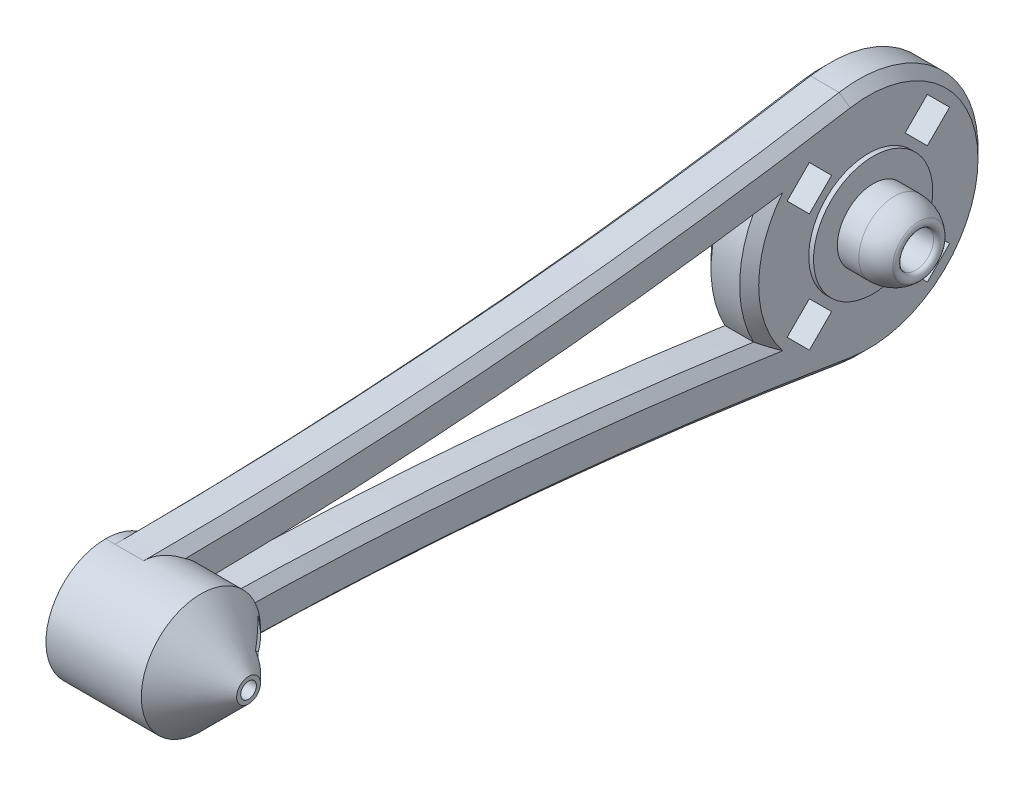
SolidWorks part; units mm, degrees
ref_plane "Front Plane" through (0, 0, 0) normal (0, 0, 1) x (1, 0, 0)
ref_plane "Top Plane" through (0, 0, 0) normal (0, 1, 0) x (1, 0, 0)
ref_plane "Right Plane" through (0, 0, 0) normal (1, 0, 0) x (0, 0, -1)
sketch "Sketch1" plane through (0, 0, 0) normal (1, 0, 0) x (0, 0, -1)
  line L0 (-150, 0) -> (0, 0) construction
  arc A0 (-4.1379, -24.6552) -> (-4.1379, 24.6552) centre (0, 0) ccw
  arc A1 (-150, 12.5) -> (-150, -12.5) centre (-150, 0) ccw
  arc A2 (-150, 12.5) -> (-4.1379, 24.6552) centre (-150, 893.75) ccw
  arc A3 (-150, -12.5) -> (-4.1379, -24.6552) centre (-150, -893.75) cw
  arc A4 (-150, 12.5) -> (-150, -12.5) centre (-150, 0) cw construction
  arc A5 (-4.1379, 24.6552) -> (-4.1379, -24.6552) centre (0, 0) ccw construction
  arc A6 (-137.77, -2.5839) -> (-22.0783, -11.7281) centre (-150, -893.75) cw
  arc A7 (-150, 2.5) -> (-2.4828, 14.7931) centre (-150, 893.75) ccw construction
  arc A8 (-137.77, 2.5839) -> (-22.0783, 11.7281) centre (-150, 893.75) ccw
  arc A9 (-137.77, 2.5839) -> (-137.77, -2.5839) centre (-150, 0) cw
  arc A10 (-150, -2.5) -> (-2.4828, -14.7931) centre (-150, -893.75) cw construction
  arc A11 (-2.4828, -14.7931) -> (-2.4828, 14.7931) centre (0, 0) ccw construction
  arc A12 (-150, 2.5) -> (-150, -2.5) centre (-150, 0) ccw construction
  arc A13 (-22.0783, 11.7281) -> (-22.0783, -11.7281) centre (0, 0) ccw
  dimension "D1" = 150
  dimension "D2" = 50
  dimension "D3" = 25
  dimension "D4" = 10
extrude "Boss-Extrude1" add sketch "Sketch1" along normal blind 10
sketch "Sketch2" plane through (10, 0, 0) normal (1, 0, 0) x (0, 0, -1)
  circle A0 centre (0, 0) radius 12.5
  dimension "D1" = 25
extrude "Boss-Extrude2" add sketch "Sketch2" along normal blind 1
sketch "Sketch3" plane through (11, 0, 0) normal (1, 0, 0) x (0, 0, -1)
  circle A0 centre (0, 0) radius 7.5
  dimension "D1" = 15
extrude "Boss-Extrude3" add sketch "Sketch3" along normal blind 12
fillet "Fillet1" radius 7.5 1 edges at (23, 0, -7.5)
sketch "Sketch4" plane through (10, 0, 0) normal (1, 0, 0) x (0, 0, -1)
  line L0 (0, 0) -> (0, 17.5) construction
  circle A0 centre (-12.3744, 12.3744) radius 2
  circle A1 centre (0, 0) radius 17.5 construction
  circle A2 centre (12.3744, 12.3744) radius 2
  circle A3 centre (12.3744, -12.3744) radius 2
  circle A4 centre (-12.3744, -12.3744) radius 2
  point P15 (0, 0)
  dimension "D1" = 35
  dimension "D3" = 4
  dimension "D2" = 45
  dimension "D4" = 4
extrude "Cut-Extrude1" cut sketch "Sketch4" against normal through all
sketch "Sketch5" plane through (10, 0, 0) normal (1, 0, 0) x (0, 0, -1)
  line L0 (-17.0413, 12.3744) -> (-12.3744, 7.7075)
  line L1 (-12.3744, 7.7075) -> (-7.7075, 12.3744)
  line L2 (-7.7075, 12.3744) -> (-12.3744, 17.0413)
  line L3 (-12.3744, 17.0413) -> (-17.0413, 12.3744)
  line L4 (-17.0413, 12.3744) -> (-7.7075, 12.3744) construction
  line L5 (-12.3744, 17.0413) -> (-12.3744, 7.7075) construction
  line L6 (-14.7078, 10.0409) -> (-10.0409, 14.7078) construction
  line L7 (7.7075, 12.3744) -> (12.3744, 7.7075)
  line L8 (12.3744, 7.7075) -> (17.0413, 12.3744)
  line L9 (17.0413, 12.3744) -> (12.3744, 17.0413)
  line L10 (12.3744, 17.0413) -> (7.7075, 12.3744)
  line L11 (12.3744, -7.7075) -> (7.7075, -12.3744)
  line L12 (7.7075, -12.3744) -> (12.3744, -17.0413)
  line L13 (12.3744, -17.0413) -> (17.0413, -12.3744)
  line L14 (17.0413, -12.3744) -> (12.3744, -7.7075)
  line L15 (-7.7075, -12.3744) -> (-12.3744, -7.7075)
  line L16 (-12.3744, -7.7075) -> (-17.0413, -12.3744)
  line L17 (-17.0413, -12.3744) -> (-12.3744, -17.0413)
  line L18 (-12.3744, -17.0413) -> (-7.7075, -12.3744)
  circle A0 centre (0, 0) radius 17.5 construction
  point P8 (-12.3744, 12.3744)
  point P25 (0, 0)
  dimension "D1" = 6.6
  dimension "D2" = 4
extrude "Cut-Extrude2" cut sketch "Sketch5" against normal blind 5
chamfer "Chamfer1" distance 2 angle 45 16 edges at (0, 0, 137.5) (0, -5.2709, 79.7751) (0, 0, 25) (0, 5.2709, 79.7751) (0, -15.5441, 76.8162) (0, 0, -25) (0, 0, 162.5) (0, 15.5441, 76.8162) (10, 15.5441, 76.8162) (10, 0, 162.5) (10, 0, -25) (10, -15.5441, 76.8162) (10, 0, 137.5) (10, -5.2709, 79.7751) (10, 0, 25) (10, 5.2709, 79.7751)
ref_plane "Plane1" through (0, 0, 150) normal (0, 0, 1) x (1, 0, 0)
sketch "Sketch7" plane through (0, 0, 150) normal (0, 0, 1) x (1, 0, 0)
  line L0 (10, -10.5) -> (10, 10.5) construction
  line L1 (10, 7.6716) -> (10, 10.5)
  line L2 (10, 10.5) -> (17.85, 2.65)
  line L3 (17.85, 2.65) -> (17.85, 1.65)
  line L4 (16.0216, 1.65) -> (10, 7.6716)
  line L5 (10, 0) -> (17.85, 0) construction
  line L6 (16.0216, 1.65) -> (17.85, 1.65)
  dimension "D1" = 45
  dimension "D2" = 2
  dimension "D3" = 3.3
  dimension "D4" = 1
revolve "Revolve1" [suppressed] add sketch "Sketch7" angle 360 about L5
sketch "Sketch8" [suppressed] plane through (10, 0, 0) normal (1, 0, 0) x (0, 0, -1)
  circle A0 centre (-150, 0) radius 7.6716
  circle A1 centre (-150, 0) radius 7.6716 construction
extrude "Cut-Extrude3" [suppressed] cut sketch "Sketch8" against normal through all
sketch "Sketch9" plane through (10, 0, 0) normal (1, 0, 0) x (0, 0, -1)
  circle A0 centre (-150, 0) radius 12.5
  circle A1 centre (-150, 0) radius 1.65
  arc A2 (-150, 12.5) -> (-150, -12.5) centre (-150, 0) ccw construction
  dimension "D1" = 3.3
extrude "Boss-Extrude4" add sketch "Sketch9" along normal blind 20 and the other way up to vertex (10 mm away) other way up to point (0, 10.5, 150)
chamfer "Chamfer2" distance 10 angle 45 1 edges at (30, 0, 137.5)
sketch "Sketch10" plane through (0, 0, 150) normal (0, 0, 1) x (1, 0, 0)
  line L0 (0, 0) -> (30, 0) construction
  line L1 (30, -1.65) -> (30, 1.65) construction
  line L2 (0, 0) -> (0, 10)
  line L3 (0, 12.5) -> (0, -12.5) construction
  line L4 (0, 10) -> (18.9645, 10)
  line L5 (18.9645, 10) -> (28.9645, 0)
  line L6 (28.9645, 0) -> (0, 0)
  line L7 (30, -2.5) -> (30, 2.5) construction
  line L8 (30, -2.5) -> (30, 2.5) construction
  point P13 (30, 2.5)
  dimension "D1" = 135
  dimension "D2" = 10
  dimension "D3" = 2.5
revolve "Cut-Revolve1" cut sketch "Sketch10" angle 360 about L0
sketch "Sketch11" plane through (0, 0, 0) normal (-1, 0, 0) x (0, 0, 1)
  line L0 (142.0761, 4.5761) -> (138.3677, 4.5761)
  line L1 (142.0761, -4.5761) -> (138.3677, -4.5761)
  line L2 (138.7761, 3.3) -> (145.3761, 3.3) construction
  line L3 (145.3761, 3.3) -> (145.3761, -3.3) construction
  line L4 (145.3761, -3.3) -> (138.7761, -3.3) construction
  line L5 (138.7761, -3.3) -> (138.7761, 3.3) construction
  line L6 (138.7761, 3.3) -> (145.3761, -3.3) construction
  line L7 (145.3761, 3.3) -> (138.7761, -3.3) construction
  line L8 (145.2463, 3.3) -> (145.2463, -3.3)
  arc A0 (142.0761, -4.5761) -> (145.2463, -3.3) centre (142.0761, 0) ccw
  arc A1 (138.3677, 4.5761) -> (138.3677, -4.5761) centre (150, 0) ccw construction
  arc A2 (138.3677, 4.5761) -> (138.3677, -4.5761) centre (150, 0) ccw
  arc A3 (145.2463, 3.3) -> (142.0761, 4.5761) centre (142.0761, 0) ccw
  point P10 (150, 0)
  dimension "D1" = 6.6
extrude "Boss-Extrude5" add sketch "Sketch11" against normal up to surface (26.7132 mm away) up to face at (20, 0, 137.5)
sketch "Sketch12" plane through (0, 0, 0) normal (-1, 0, 0) x (0, 0, 1)
  circle A0 centre (142.0761, 0) radius 2
  arc A1 (142.0761, -4.5761) -> (145.2463, -3.3) centre (142.0761, 0) ccw construction
  dimension "D1" = 4
extrude "Cut-Extrude4" cut sketch "Sketch12" against normal through all
sketch "Sketch14" plane through (0, 0, 0) normal (-1, 0, 0) x (0, 0, 1)
  line L1 (145.3761, -3.3) -> (138.7761, -3.3)
  line L2 (145.3761, -3.3) -> (145.3761, 3.3)
  line L3 (145.3761, 3.3) -> (138.7761, 3.3)
  line L4 (138.7761, -3.3) -> (138.7761, 3.3)
  line L5 (145.3761, -3.3) -> (138.7761, 3.3) construction
  line L6 (145.3761, 3.3) -> (138.7761, -3.3) construction
  circle A0 centre (142.0761, 0) radius 2 construction
  point P0 (142.0761, 0)
  dimension "D2" = 6.6
extrude "Cut-Extrude5" cut sketch "Sketch14" against normal through all from offset 10 offset against normal yes
sketch "Sketch15" plane through (0, 0, 0) normal (-1, 0, 0) x (0, 0, 1)
  circle A0 centre (0, 0) radius 3.75
  dimension "D1" = 7.5
extrude "Cut-Extrude6" cut sketch "Sketch15" against normal through all
fillet "Fillet3" radius 1 1 edges at (21.9952, 0, 3.75)
